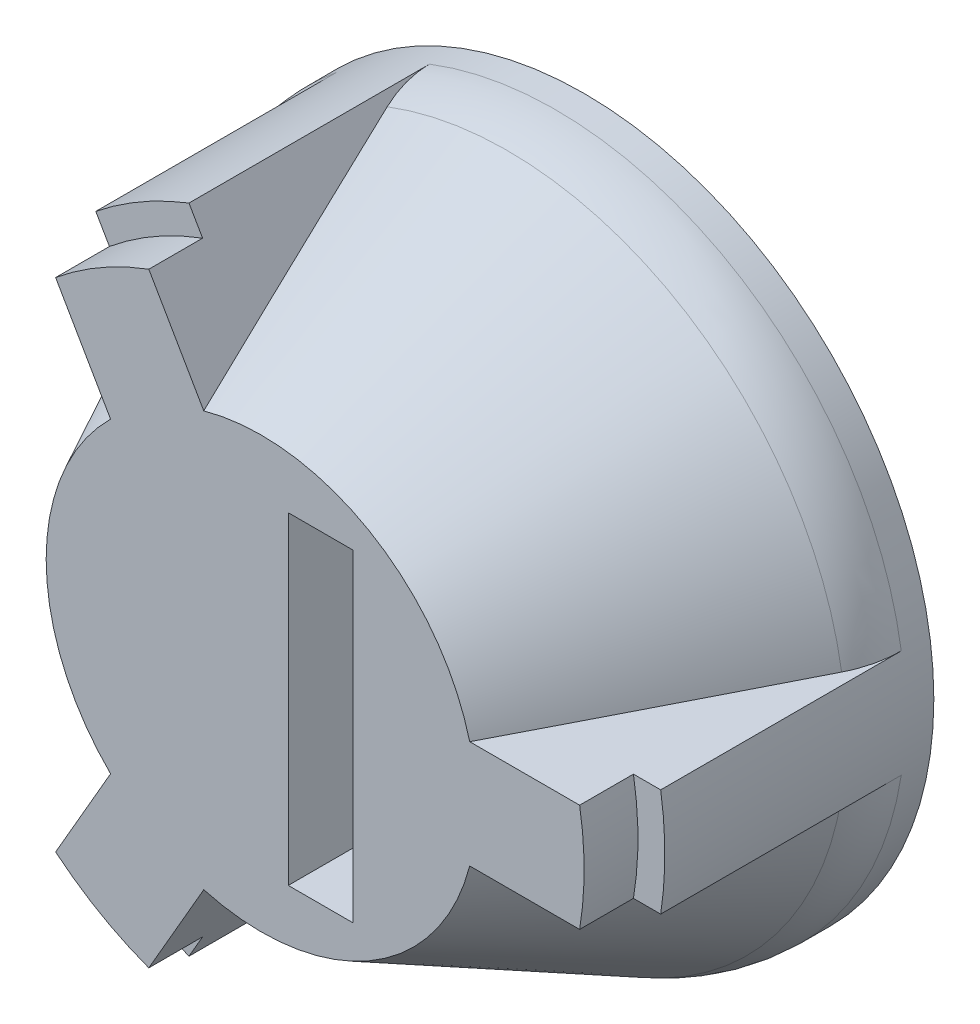
SolidWorks part; units mm, degrees
ref_plane "Plan de face" through (0, 0, 0) normal (0, 0, 1) x (1, 0, 0)
ref_plane "Plan de dessus" through (0, 0, 0) normal (0, 1, 0) x (1, 0, 0)
ref_plane "Plan de droite" through (0, 0, 0) normal (1, 0, 0) x (0, 0, -1)
sketch "Esquisse1" plane through (0, 0, 0) normal (0, 0, 1) x (1, 0, 0)
  line L0 (0, 0) -> (14, 0) construction
  line L1 (0, 0) -> (-7, 12.1244) construction
  line L2 (0, 0) -> (-7, -12.1244) construction
  line L3 (13.8564, 2) -> (7.746, 2)
  line L4 (13.8564, -2) -> (7.746, -2)
  line L5 (-5.1962, -13) -> (-2.1409, -7.7082)
  line L6 (-8.6603, -11) -> (-5.605, -5.7082)
  line L7 (-8.6603, 11) -> (-5.605, 5.7082)
  line L8 (-5.1962, 13) -> (-2.1409, 7.7082)
  circle A0 centre (0, 0) radius 14 construction
  circle A1 centre (0, 0) radius 8 construction
  circle A2 centre (0, 0) radius 8 construction
  arc A3 (13.8564, 2) -> (13.8564, -2) centre (0, 0) cw
  arc A4 (7.746, -2) -> (4, -6.9282) centre (0, 0) cw
  arc A5 (7.746, 2) -> (4, 6.9282) centre (0, 0) ccw
  arc A6 (-2.1409, -7.7082) -> (4, -6.9282) centre (0, 0) ccw
  arc A7 (-5.1962, -13) -> (-8.6603, -11) centre (0, 0) cw
  arc A8 (-5.605, -5.7082) -> (-8, 0) centre (0, 0) cw
  arc A9 (-5.605, 5.7082) -> (-8, 0) centre (0, 0) ccw
  arc A10 (-8.6603, 11) -> (-5.1962, 13) centre (0, 0) cw
  arc A11 (-2.1409, 7.7082) -> (4, 6.9282) centre (0, 0) cw
  point P30 (0, 0)
  dimension "D1" = 28
  dimension "D2" = 16
  dimension "D3" = 16
  dimension "D4" = 120
  dimension "D5" = 4
  dimension "D6" = 3
extrude "Boss.-Extru.1" add sketch "Esquisse1" along normal blind 12 contours A11 L8 A10 L7 A9 A8 L6 A7 L5 A6 A4 L4 A3 L3 A5 region at (0, 0, 0)
sketch "Esquisse4" plane through (0, 0, 0) normal (0, 1, 0) x (1, 0, 0)
  line L0 (14, 0) -> (8, -12)
  line L1 (8, -12) -> (0, -12)
  line L2 (-2.1409, -12) -> (7.746, -12) construction
  line L3 (0, -12) -> (0, 0)
  line L4 (0, 0) -> (14, 0)
  line L5 (14, 0) -> (13.8564, 0) construction
  line L6 (13.8564, -12) -> (7.746, -12) construction
  dimension "D1" = 8
revolve "Révolution1" add sketch "Esquisse4" angle 360 about L3
sketch "Esquisse5" plane through (0, 0, 0) normal (0, 0, -1) x (-1, 0, 0)
  circle A0 centre (0, 0) radius 12.2
  dimension "D1" = 24.4
extrude "Enlèv. mat.-Extru.1" cut sketch "Esquisse5" against normal blind 2.5
sketch "Esquisse6" plane through (0, 0, 0) normal (0, 1, 0) x (1, 0, 0)
  line L0 (13, 0) -> (15.4808, 0)
  line L1 (13.8564, 0) -> (-5.1962, 0) construction
  line L2 (15.4808, 0) -> (15.4808, -12)
  line L3 (15.4808, -12) -> (13, -12)
  line L4 (13, -12) -> (13, 0) construction
  line L5 (14, -12) -> (14, 0) construction
  line L6 (0, 0) -> (0, -12) construction
  line L7 (-2.1409, -12) -> (7.746, -12) construction
  line L8 (13.8564, -12) -> (7.746, -12) construction
  line L9 (13.8564, -12) -> (7.746, -12) construction
  line L10 (13, 0) -> (13, -10)
  line L11 (13, -10) -> (12, -10)
  line L12 (12, -10) -> (12, -12)
  line L13 (12, -12) -> (13, -12)
  dimension "D1" = 1
  dimension "D2" = 1
  dimension "D3" = 2
revolve "Enlèvement de matière-Révolution1" cut sketch "Esquisse6" angle 360 about L6
fillet "Congé2" radius 4 3 edges at (-13, 0, 2) (6.5, -11.2583, 2) (6.5, 11.2583, 2)
sketch "Esquisse7" plane through (0, 0, 12) normal (0, 0, 1) x (1, 0, 0)
  line L0 (1, 6) -> (3.4, 6)
  line L1 (3.4, 6) -> (3.4, -6)
  line L2 (3.4, -6) -> (1, -6)
  line L3 (1, -6) -> (1, 6)
  line L4 (0, 0) -> (12, 0) construction
  arc A2 (11.8322, -2) -> (11.8322, 2) centre (0, 0) ccw construction
  point P7 (12, 0)
  dimension "D1" = 12
  dimension "D2" = 12
  dimension "D3" = 2.4
  dimension "D4" = 1
extrude "Enlèv. mat.-Extru.2" cut sketch "Esquisse7" against normal blind 5
